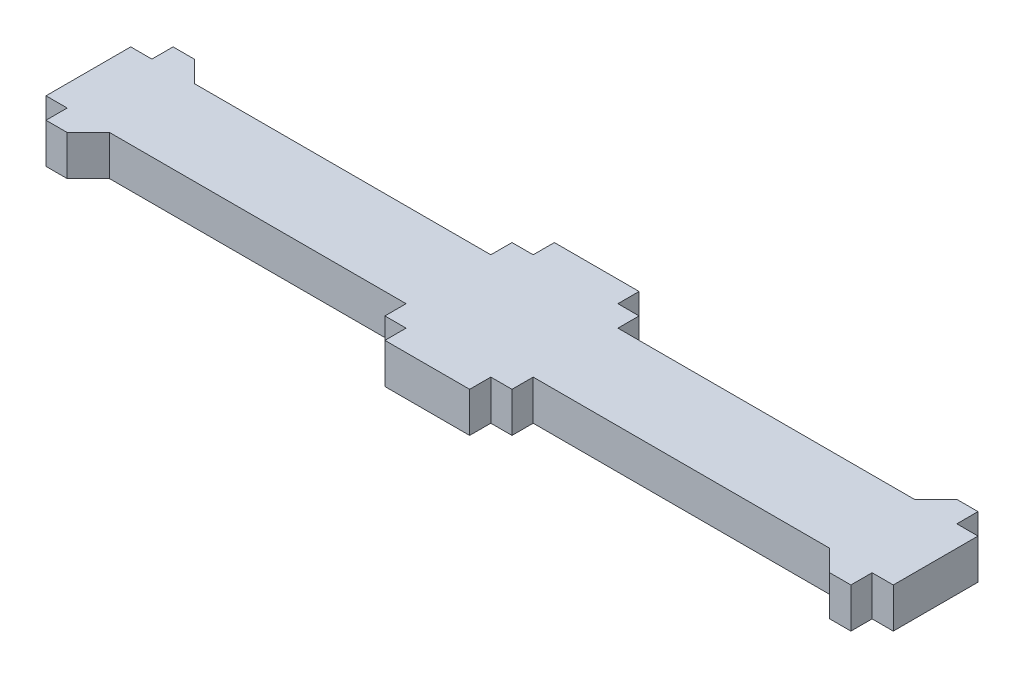
SolidWorks part; units mm, degrees
ref_plane "Front Plane" through (0, 0, 0) normal (0, 0, 1) x (1, 0, 0)
ref_plane "Top Plane" through (0, 0, 0) normal (0, 1, 0) x (1, 0, 0)
ref_plane "Right Plane" through (0, 0, 0) normal (1, 0, 0) x (0, 0, -1)
sketch "Sketch1" plane through (0, 0, 0) normal (0, 1, 0) x (1, 0, 0)
  line L0 (-63.5, 12.7) -> (-63.5, 0) construction
  line L1 (-53.975, 0) -> (-6.35, 0)
  line L2 (0, 0) -> (0, 12.7)
  line L3 (-3.175, 0) -> (0, 0)
  line L4 (-127, 0) -> (-127, 12.7)
  line L5 (-73.025, 12.7) -> (-120.65, 12.7)
  line L6 (-123.825, 12.7) -> (-123.825, 15.875)
  line L7 (-123.825, 15.875) -> (-120.65, 15.875)
  line L8 (-120.65, 12.7) -> (-120.65, 15.875)
  line L9 (0, 6.35) -> (-127, 6.35) construction
  line L10 (-123.825, 12.7) -> (-127, 12.7)
  line L11 (-69.85, -3.175) -> (-69.85, -6.35)
  line L12 (-57.15, -6.35) -> (-69.85, -6.35)
  line L13 (-69.85, 15.875) -> (-73.025, 15.875)
  line L14 (-73.025, 12.7) -> (-73.025, 15.875)
  line L15 (-63.5, 15.875) -> (-63.5, 19.05)
  line L16 (-57.15, 19.05) -> (-69.85, 19.05)
  line L17 (-69.85, 15.875) -> (-69.85, 19.05)
  line L18 (-63.5, -3.175) -> (-63.5, -6.35)
  line L19 (-73.025, 0) -> (-73.025, -3.175)
  line L20 (-69.85, -3.175) -> (-73.025, -3.175)
  line L21 (-123.825, 0) -> (-127, 0)
  line L22 (-120.65, 0) -> (-120.65, -3.175)
  line L23 (-123.825, -3.175) -> (-120.65, -3.175)
  line L24 (-123.825, 0) -> (-123.825, -3.175)
  line L25 (-73.025, 0) -> (-120.65, 0)
  line L26 (-123.825, 0) -> (-127, 0)
  line L27 (-73.025, 0) -> (-120.65, 0)
  line L28 (-53.975, 0) -> (-6.35, 0)
  line L29 (-3.175, 0) -> (-3.175, -3.175)
  line L30 (-3.175, -3.175) -> (-6.35, -3.175)
  line L31 (-6.35, 0) -> (-6.35, -3.175)
  line L32 (-3.175, 0) -> (0, 0)
  line L33 (-57.15, -3.175) -> (-53.975, -3.175)
  line L34 (-53.975, 0) -> (-53.975, -3.175)
  line L35 (-57.15, 15.875) -> (-57.15, 19.05)
  line L36 (-53.975, 12.7) -> (-53.975, 15.875)
  line L37 (-57.15, 15.875) -> (-53.975, 15.875)
  line L38 (-57.15, -3.175) -> (-57.15, -6.35)
  line L39 (-3.175, 12.7) -> (0, 12.7)
  line L40 (-6.35, 12.7) -> (-6.35, 15.875)
  line L41 (-3.175, 15.875) -> (-6.35, 15.875)
  line L42 (-3.175, 12.7) -> (-3.175, 15.875)
  line L43 (-53.975, 12.7) -> (-6.35, 12.7)
  dimension "D1" = 127
  dimension "D2" = 12.7
  dimension "D3" = 3.175
  dimension "D4" = 3.175
  dimension "D5" = 3.175
  dimension "D6" = 9.525
  dimension "D7" = 3.175
  dimension "D8" = 6.35
  dimension "D9" = 3.175
extrude "Boss-Extrude1" add sketch "Sketch1" along normal blind 5.9944 contours L43 L36 L37 L35 L16 L17 L13 L14 L5 L8 L7 L6 L10 L4 L21 L24 L23 L22 L25 L19 L20 L11 L12 L38 L33 L34 L1 L31 L30 L29 L3 L2 L39 L42 L41 L40 region at (-63.5, 0, -6.35)
chamfer "Chamfer1" distance 3.175 angle 45 4 edges at (-6.35, 2.9972, -12.7) (-6.35, 2.9972, 0) (-120.65, 2.9972, 0) (-120.65, 2.9972, -12.7)
